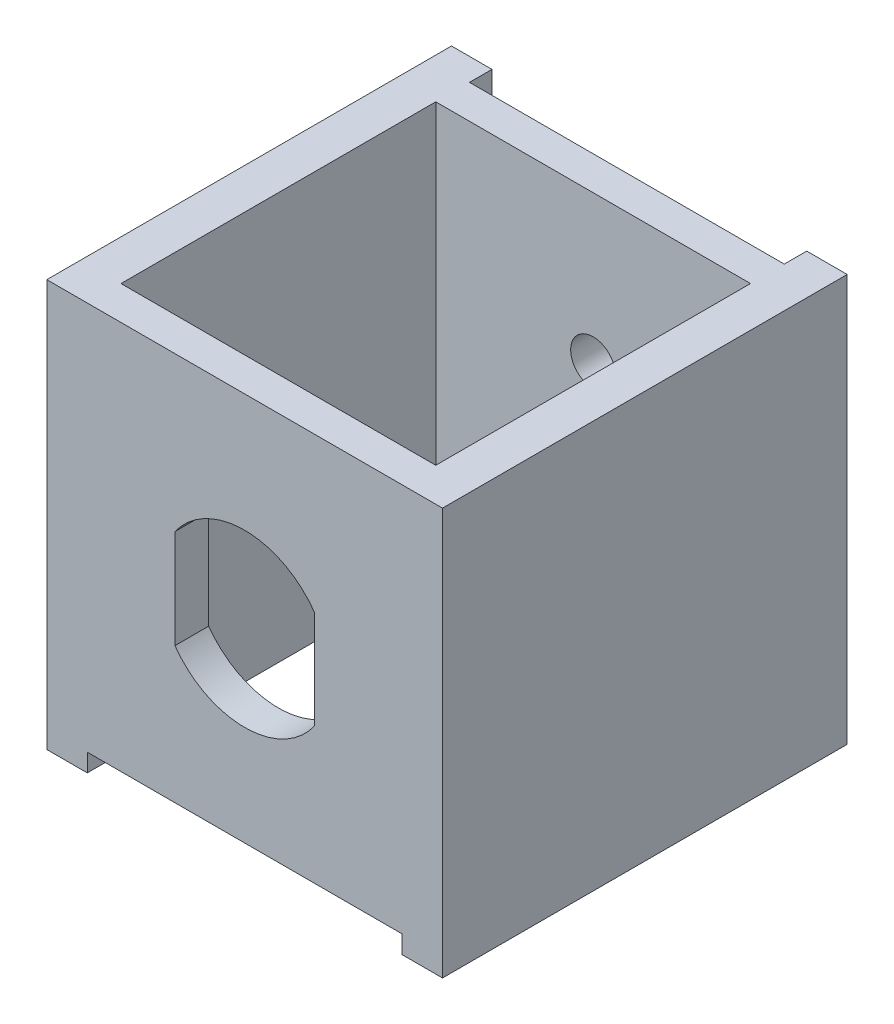
SolidWorks part; units mm, degrees
ref_plane "Спереди" through (0, 0, 0) normal (0, 0, 1) x (1, 0, 0)
ref_plane "Сверху" through (0, 0, 0) normal (0, 1, 0) x (1, 0, 0)
ref_plane "Справа" through (0, 0, 0) normal (1, 0, 0) x (0, 0, -1)
sketch "Эскиз1" plane through (0, 0, 0) normal (0, 0, 1) x (1, 0, 0)
  line L0 (0, 9.25) -> (0, -9.25) construction
  line L1 (-9, 9.25) -> (9, 9.25)
  line L2 (-9, 9.25) -> (-9, -9.25)
  line L3 (-9, -9.25) -> (9, -9.25)
  line L4 (9, 9.25) -> (9, -9.25)
  line L13 (3.1, -2.1977) -> (3.1, 2.1977)
  line L14 (-3.1, 2.1977) -> (-3.1, -2.1977)
  line L15 (3.1, -2.1977) -> (3.1, 2.1977)
  line L16 (-3.1, 2.1977) -> (-3.1, -2.1977)
  arc A8 (-3.1, -2.1977) -> (3.1, -2.1977) centre (0, 0) ccw
  arc A9 (3.1, 2.1977) -> (-3.1, 2.1977) centre (0, 0) ccw
  arc A10 (-3.1, -2.1977) -> (3.1, -2.1977) centre (0, 0) ccw
  arc A11 (3.1, 2.1977) -> (-3.1, 2.1977) centre (0, 0) ccw
  dimension "D1" = 18.5
  dimension "D2" = 18
  dimension "D3" = 0.2
extrude "Бобышка-Вытянуть1" add sketch "Эскиз1" against normal blind 1.5
sketch "Эскиз2" plane through (0, 0, 0) normal (0, 0, 1) x (1, 0, 0)
  line L0 (-9, -9.25) -> (9, -9.25) construction
  line L1 (-9, 9.25) -> (-7, 9.25)
  line L2 (-9, 9.25) -> (-9, -9.25)
  line L3 (-9, -9.25) -> (-7, -9.25)
  line L4 (-7, 9.25) -> (-7, -9.25)
  line L5 (0, -50) -> (0, 50) construction
  line L6 (7, 9.25) -> (7, -9.25)
  line L7 (9, -9.25) -> (7, -9.25)
  line L8 (9, 9.25) -> (9, -9.25)
  line L9 (9, 9.25) -> (7, 9.25)
  dimension "D1" = 2
extrude "Бобышка-Вытянуть2" add sketch "Эскиз2" against normal blind 18
sketch "Эскиз3" plane through (0, 0, -18) normal (0, 0, -1) x (-1, 0, 0)
  line L0 (-9, -9.25) -> (-9, 9.25) construction
  line L1 (-9, 2) -> (9, 2)
  line L2 (-9, 2) -> (-9, -2)
  line L3 (-9, -2) -> (9, -2)
  line L4 (9, 2) -> (9, -2)
  line L5 (9, 9.25) -> (9, -9.25) construction
  line L6 (-9, 0) -> (0, 0) construction
  dimension "D1" = 4
extrude "Бобышка-Вытянуть3" [suppressed] add sketch "Эскиз3" against normal blind 2 from offset 2 offset against normal yes
sketch "Эскиз4" plane through (-9, 0, 0) normal (-1, 0, 0) x (0, 0, 1)
  line L0 (0, 0) -> (-18, 0) construction
  line L1 (0, 9.25) -> (0, -9.25) construction
  line L2 (-18, 9.25) -> (-18, -9.25) construction
  line L3 (-9, 1.5) -> (-9, -1.5) construction
  line L4 (-11.5, 1.5) -> (-6.5, 1.5)
  line L5 (-11.5, 1.5) -> (-11.5, -1.5)
  line L6 (-11.5, -1.5) -> (-6.5, -1.5)
  line L7 (-6.5, 1.5) -> (-6.5, -1.5)
  line L8 (-9, 0) -> (-9, 9.25) construction
  line L9 (-18, 9.25) -> (0, 9.25) construction
  line L10 (-6.5, 1.5) -> (0, 1.5) construction
  point P10 (-6.5, 0)
  point P13 (-9, 0)
  dimension "D1" = 3
  dimension "D2" = 5
sketch "Эскиз5" plane through (0, 9.25, 0) normal (0, 1, 0) x (1, 0, 0)
  line L0 (9, 18) -> (9, 0) construction
  line L1 (9, 17) -> (-9, 17)
  line L2 (9, 17) -> (9, 15.5)
  line L3 (9, 15.5) -> (-9, 15.5)
  line L4 (-9, 17) -> (-9, 15.5)
  line L5 (-9, 0) -> (-9, 18) construction
  line L6 (9, 18) -> (7, 18) construction
  dimension "D1" = 1.5
  dimension "D2" = 1
extrude "Бобышка-Вытянуть5" add sketch "Эскиз5" against normal blind 15
sketch "Эскиз6" plane through (0, 0, -15.5) normal (0, 0, -1) x (-1, 0, 0)
  line L0 (0, 1.5) -> (0, -1.5) construction
  circle A0 centre (0, 2.5) radius 1
  circle A1 centre (0, -2.5) radius 1
  dimension "D1" = 2
  dimension "D2" = 3
extrude "Вырез-Вытянуть1" cut sketch "Эскиз6" along normal through all
sketch "Эскиз7" plane through (0, -9.25, 0) normal (0, -1, 0) x (1, 0, 0)
  line L0 (-9, 0) -> (9, 0) construction
  line L1 (-7, -1.5) -> (7, -1.5)
  line L2 (-7, -1.5) -> (-7, 0)
  line L3 (-7, 0) -> (7, 0)
  line L4 (7, -1.5) -> (7, 0)
extrude "Вырез-Вытянуть2" cut sketch "Эскиз7" against normal blind 1
sketch "Эскиз8" plane through (0, 0, 0) normal (0, 0, 1) x (1, 0, 0)
  line L6 (-8.8, -9.05) -> (8.8, -9.05)
  line L7 (8.8, -9.05) -> (9, -9.05) construction
  line L8 (9, -9.25) -> (9, 9.25) construction
  line L9 (8.8, -9.25) -> (8.8, 9.05)
  line L10 (-8.8, 9.05) -> (-8.8, -9.25)
  line L11 (8.8, 9.05) -> (-8.8, 9.05)
  line L12 (8.8, -9.05) -> (8.8, 9.05)
  line L13 (-8.8, 9.05) -> (-8.8, -9.05)
  line L14 (8.8, 9.05) -> (-8.8, 9.05)
  line L15 (8.8, -9.05) -> (8.8, -9.25) construction
  line L16 (7, -9.25) -> (9, -9.25) construction
  line L17 (13.8, 14.05) -> (-13.8, 14.05)
  line L18 (-13.8, 14.05) -> (-13.8, -14.05)
  line L19 (-13.8, -14.05) -> (13.8, -14.05)
  line L20 (13.8, -14.05) -> (13.8, 14.05)
  dimension "D2" = 5
  dimension "D1" = 0.2
extrude "Вырез-Вытянуть3" cut sketch "Эскиз8" against normal through all
extrude "Бобышка-Вытянуть4" add sketch "Эскиз4" along normal blind 1.5 and the other way up to next
fillet "Скругление1" radius 0.4 2 edges at (-10.5, 0, -6.5) (-10.5, 0, -11.5)
